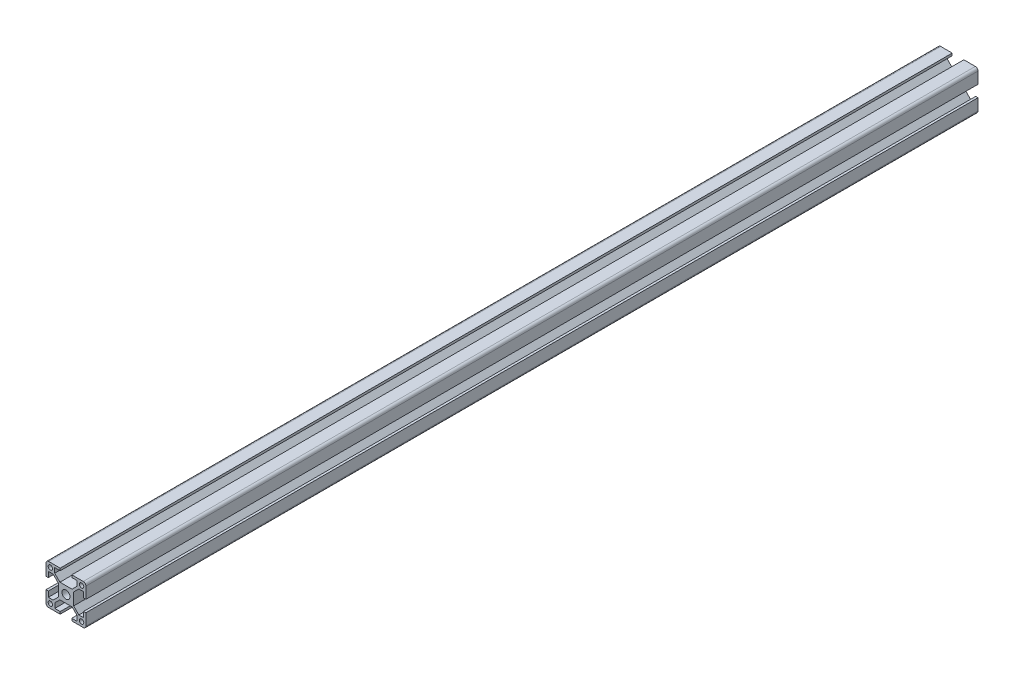
SolidWorks part; units mm, degrees
ref_plane "Front Plane" through (0, 0, 0) normal (0, 0, 1) x (1, 0, 0)
ref_plane "Top Plane" through (0, 0, 0) normal (0, 1, 0) x (1, 0, 0)
ref_plane "Right Plane" through (0, 0, 0) normal (1, 0, 0) x (0, 0, -1)
sketch "Sketch1" plane through (0, 0, 0) normal (0, 0, 1) x (1, 0, 0)
  line L0 (-8.46, 9.66) -> (-4.55, 5.75)
  line L1 (-15, -15) -> (-4.35, -15)
  line L2 (-15, -15) -> (-15, -4.35)
  line L3 (-15, 15) -> (-4.35, 15)
  line L4 (15, -15) -> (15, -4.35)
  line L5 (-15, -15) -> (15, 15) construction
  line L6 (-15, 15) -> (15, -15) construction
  line L7 (-4.5783, -5.75) -> (4.6181, -5.75)
  line L8 (-5.75, -4.55) -> (-5.75, 4.55)
  line L9 (-4.55, 5.75) -> (4.55, 5.75)
  line L10 (5.75, -4.55) -> (5.75, 4.55)
  line L11 (-5.75, -5.75) -> (5.75, 5.75) construction
  line L12 (-5.75, 5.75) -> (5.75, -5.75) construction
  line L13 (-8.46, 9.66) -> (-8.46, 13.26)
  line L14 (-8.46, 13.26) -> (-4.35, 13.26)
  line L15 (-4.35, 13.26) -> (-4.35, 15)
  line L16 (-9.66, 8.46) -> (-5.75, 4.55)
  line L17 (-9.66, 8.46) -> (-13.26, 8.46)
  line L18 (-13.26, 8.46) -> (-13.26, 4.35)
  line L19 (-13.26, 4.35) -> (-15, 4.35)
  line L20 (9.66, 8.46) -> (5.75, 4.55)
  line L21 (8.46, 9.66) -> (8.46, 13.26)
  line L22 (8.46, 13.26) -> (4.35, 13.26)
  line L23 (4.35, 13.26) -> (4.35, 15)
  line L24 (8.46, 9.66) -> (4.55, 5.75)
  line L25 (9.66, 8.46) -> (13.26, 8.46)
  line L26 (13.26, 8.46) -> (13.26, 4.35)
  line L27 (13.26, 4.35) -> (15, 4.35)
  line L28 (9.66, -8.46) -> (5.75, -4.55)
  line L29 (-9.66, -8.46) -> (-13.26, -8.46)
  line L30 (-13.26, -8.46) -> (-13.26, -4.35)
  line L31 (-13.26, -4.35) -> (-15, -4.35)
  line L32 (-9.66, -8.46) -> (-5.75, -4.55)
  line L33 (-8.4202, -9.5919) -> (-8.4202, -13.26)
  line L34 (-8.4202, -13.26) -> (-4.35, -13.26)
  line L35 (-4.35, -13.26) -> (-4.35, -15)
  line L36 (-8.4202, -9.5919) -> (-4.5783, -5.75)
  line L37 (9.66, -8.46) -> (13.26, -8.46)
  line L38 (13.26, -8.46) -> (13.26, -4.35)
  line L39 (13.26, -4.35) -> (15, -4.35)
  line L40 (8.46, -9.5919) -> (4.6181, -5.75)
  line L41 (8.46, -9.5919) -> (8.46, -13.26)
  line L42 (8.46, -13.26) -> (4.35, -13.26)
  line L43 (4.35, -13.26) -> (4.35, -15)
  line L44 (-15, 4.35) -> (-15, 15)
  line L45 (15, 4.35) -> (15, 15)
  line L46 (4.35, -15) -> (15, -15)
  line L47 (4.35, 15) -> (15, 15)
  circle A0 centre (0, 0) radius 3
  circle A1 centre (11.73, 11.73) radius 1.65
  circle A2 centre (11.73, -11.73) radius 1.65
  circle A3 centre (-11.73, -11.73) radius 1.65
  circle A4 centre (-11.73, 11.73) radius 1.65
  point P0 (0, 0)
  point P63 (0, 0)
  dimension "D3" = 6
  dimension "D10" = 3.3
  dimension "D1" = 30
  dimension "D2" = 30
  dimension "D4" = 11.5
  dimension "D5" = 11.5
  dimension "D6" = 10.65
  dimension "D7" = 4.11
  dimension "D8" = 1.74
  dimension "D9" = 3.6
  dimension "D11" = 3.27
  dimension "D12" = 3.27
  dimension "D13" = 3.27
  dimension "D14" = 3.27
  dimension "D15" = 3.27
  dimension "D16" = 3.27
  dimension "D17" = 3.27
  dimension "D18" = 3.27
extrude "Boss-Extrude1" add sketch "Sketch1" along normal blind 670
fillet "Fillet1" radius 2 4 edges at (-15, -15, 335) (15, -15, 335) (15, 15, 335) (-15, 15, 335)
